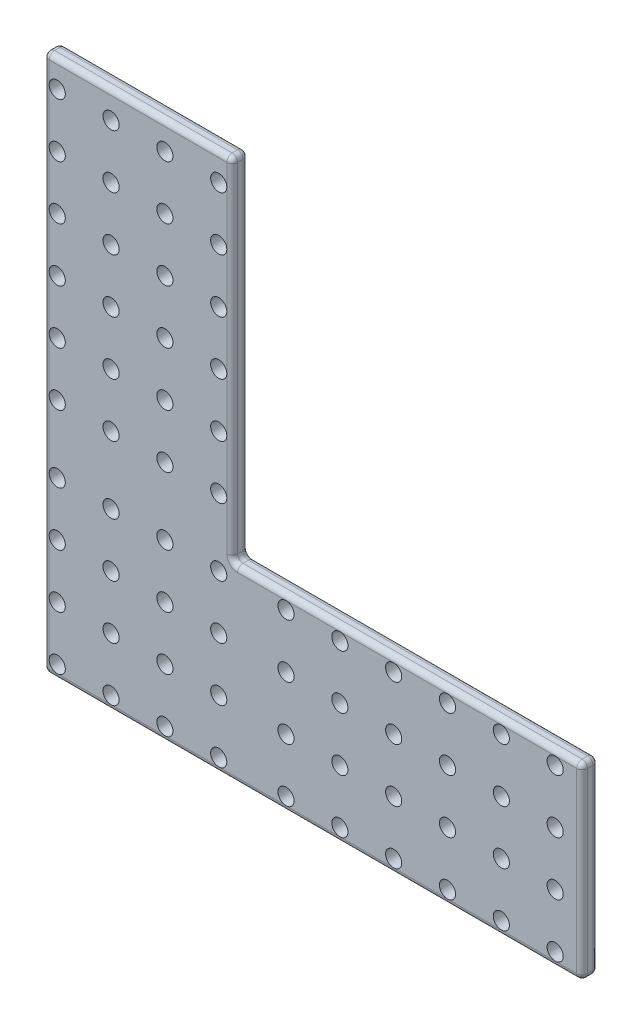
SolidWorks part; units mm, degrees
ref_plane "Plan de face" through (0, 0, 0) normal (0, 0, 1) x (1, 0, 0)
ref_plane "Plan de dessus" through (0, 0, 0) normal (0, 1, 0) x (1, 0, 0)
ref_plane "Plan de droite" through (0, 0, 0) normal (1, 0, 0) x (0, 0, -1)
sketch "Esquisse1" plane through (0, 0, 0) normal (0, 0, 1) x (1, 0, 0)
  line L1 (0, 0) -> (100, 0)
  line L2 (0, 0) -> (0, 35)
  line L3 (0, 35) -> (100, 35)
  line L4 (100, 0) -> (100, 35)
  dimension "D1" = 100
  dimension "D2" = 35
extrude "Boss.-Extru.1" add sketch "Esquisse1" along normal blind 3
sketch "Esquisse2" plane through (0, 0, 3) normal (0, 0, 1) x (1, 0, 0)
  line L0 (100, 35) -> (0, 35) construction
  line L1 (100, 0) -> (100, 35) construction
  circle A0 centre (95, 32.5) radius 1.5
  circle A1 centre (85, 32.5) radius 1.5
  circle A2 centre (75, 32.5) radius 1.5
  circle A3 centre (65, 32.5) radius 1.5
  circle A4 centre (55, 32.5) radius 1.5
  circle A5 centre (45, 32.5) radius 1.5
  circle A10 centre (85, 22.5) radius 1.5
  circle A11 centre (75, 22.5) radius 1.5
  circle A12 centre (65, 22.5) radius 1.5
  circle A13 centre (55, 22.5) radius 1.5
  circle A14 centre (45, 22.5) radius 1.5
  circle A19 centre (85, 12.5) radius 1.5
  circle A20 centre (75, 12.5) radius 1.5
  circle A21 centre (65, 12.5) radius 1.5
  circle A22 centre (55, 12.5) radius 1.5
  circle A23 centre (45, 12.5) radius 1.5
  circle A28 centre (85, 2.5) radius 1.5
  circle A29 centre (75, 2.5) radius 1.5
  circle A30 centre (65, 2.5) radius 1.5
  circle A31 centre (55, 2.5) radius 1.5
  circle A32 centre (45, 2.5) radius 1.5
  circle A37 centre (95, 22.5) radius 1.5
  circle A38 centre (95, 12.5) radius 1.5
  circle A39 centre (95, 2.5) radius 1.5
  circle A40 centre (15, 12.5) radius 1.5 [skipped]
  circle A41 centre (5, 12.5) radius 1.5 [skipped]
  circle A42 centre (15, 2.5) radius 1.5 [skipped]
  circle A43 centre (5, 2.5) radius 1.5 [skipped]
  circle A44 centre (25, 32.5) radius 1.5 [skipped]
  circle A45 centre (15, 32.5) radius 1.5 [skipped]
  circle A46 centre (5, 32.5) radius 1.5 [skipped]
  circle A47 centre (25, 22.5) radius 1.5 [skipped]
  circle A48 centre (15, 22.5) radius 1.5 [skipped]
  circle A49 centre (5, 22.5) radius 1.5 [skipped]
  circle A50 centre (25, 12.5) radius 1.5 [skipped]
  circle A51 centre (25, 2.5) radius 1.5 [skipped]
  circle A52 centre (35, 32.5) radius 1.5 [skipped]
  circle A53 centre (35, 22.5) radius 1.5 [skipped]
  circle A54 centre (35, 12.5) radius 1.5 [skipped]
  circle A55 centre (35, 2.5) radius 1.5 [skipped]
  dimension "D1" = 2.5
  dimension "D2" = 3
  dimension "D3" = 5
  dimension "D4" = 10
  dimension "D5" = 4
extrude "Enlèv. mat.-Extru.1" cut sketch "Esquisse2" against normal blind 3
fillet "Congé1" radius 1 4 edges at (0, 35, 1.5) (0, 0, 1.5) (100, 0, 1.5) (100, 35, 1.5)
sketch "Esquisse3" plane through (0, 0, 3) normal (0, 0, 1) x (1, 0, 0)
  line L0 (0, 17.5) -> (17.5, 17.5) construction
  line L1 (0, 34) -> (0, 1) construction
  line L2 (17.5, 17.5) -> (17.5, 0) construction
  line L3 (1, 0) -> (99, 0) construction
  dimension "D1" = 17.5
  dimension "D2" = 17.5
ref_axis "Axe1" through (17.5, 17.5, 3) along (0, 0, 1)
pattern_circular "Répétition circulaire4" count 2 over 90 about axis through (17.5, 17.5, 3) along (0, 0, 1) of "Boss.-Extru.1", "Enlèv. mat.-Extru.1", "Congé1"
sketch "Esquisse4" plane through (0, 0, 3) normal (0, 0, 1) x (1, 0, 0)
  line L0 (35, 35) -> (35, 0) construction
  line L1 (1, 0) -> (99, 0) construction
  line L2 (35, 0) -> (35, 35) construction
  line L3 (35, 35) -> (0, 35) construction
  line L4 (0, 99) -> (0, 1) construction
  circle A1 centre (2.5, 2.5) radius 1.5
  circle A3 centre (2.5, 45) radius 1.5 construction
  circle A4 centre (45, 2.5) radius 1.5 construction
  circle A5 centre (12.5, 2.5) radius 1.5
  circle A6 centre (22.5, 2.5) radius 1.5
  circle A7 centre (32.5, 2.5) radius 1.5
  circle A8 centre (12.5, 12.5) radius 1.5
  circle A9 centre (22.5, 12.5) radius 1.5
  circle A10 centre (32.5, 12.5) radius 1.5
  circle A11 centre (12.5, 22.5) radius 1.5
  circle A12 centre (22.5, 22.5) radius 1.5
  circle A13 centre (32.5, 22.5) radius 1.5
  circle A14 centre (12.5, 32.5) radius 1.5
  circle A15 centre (22.5, 32.5) radius 1.5
  circle A16 centre (32.5, 32.5) radius 1.5
  circle A17 centre (2.5, 12.5) radius 1.5
  circle A18 centre (2.5, 22.5) radius 1.5
  circle A19 centre (2.5, 32.5) radius 1.5
  dimension "D1" = 0
  dimension "D2" = 0
  dimension "D3" = 3
  dimension "D4" = 4
  dimension "D5" = 4
extrude "Enlèv. mat.-Extru.2" cut sketch "Esquisse4" against normal blind 10
fillet "Congé2" radius 1 11 edges at (50, 0, 0) (99.7071, 0.2929, 0) (100, 17.5, 0) (99.7071, 34.7071, 0) (50, 0, 3) (99.7071, 0.2929, 3) (100, 17.5, 3) (99.7071, 34.7071, 3) (67, 35, 0) (67, 35, 3) (35, 35, 1.5)
